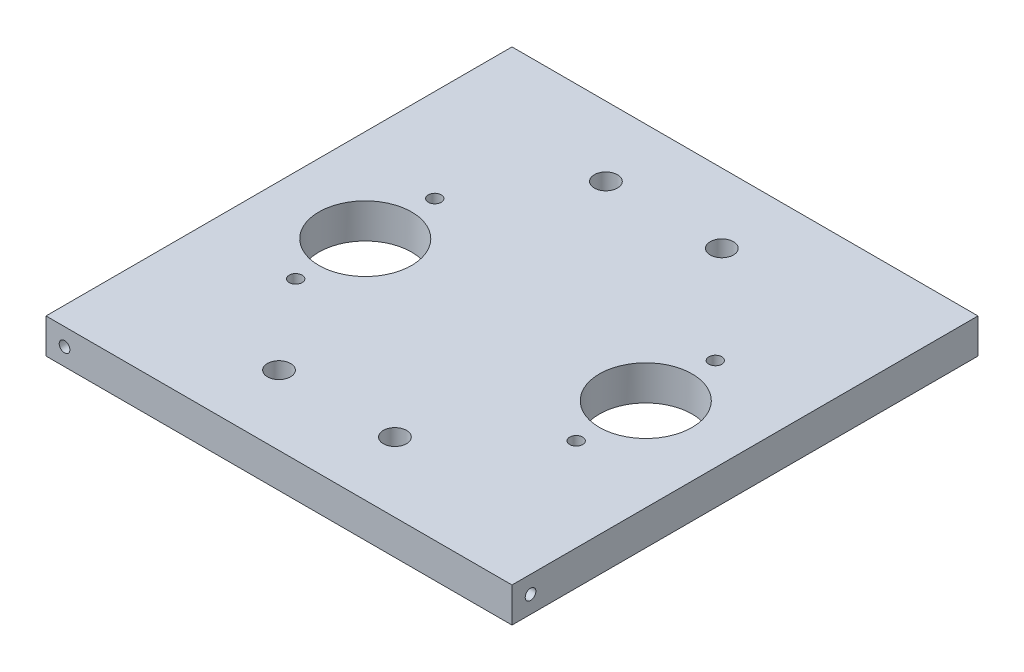
SolidWorks part; units mm, degrees
material "6061 Alloy"
ref_plane "Front" through (0, 0, 0) normal (0, 0, 1) x (1, 0, 0)
ref_plane "Top" through (0, 0, 0) normal (0, 1, 0) x (1, 0, 0)
ref_plane "Right" through (0, 0, 0) normal (1, 0, 0) x (0, 0, -1)
sketch "Sketch1" plane through (0, 0, 0) normal (0, 1, 0) x (1, 0, 0)
  line L1 (0, 0) -> (127.635, 0)
  line L2 (0, 0) -> (0, 127.635)
  line L3 (0, 127.635) -> (127.635, 127.635)
  line L4 (127.635, 0) -> (127.635, 127.635)
  dimension "D1" = 127.635
  dimension "D2" = 127.635
extrude "Main Plate" add sketch "Sketch1" along normal blind 9.525
sketch "Sketch2" plane through (0, 9.525, 0) normal (0, 1, 0) x (1, 0, 0)
  line L0 (0, 127.635) -> (0, 0) construction
  line L1 (127.635, 127.635) -> (0, 127.635) construction
  circle A0 centre (44.7675, 108.585) radius 3.175
  dimension "D1" = 6.35
  dimension "D2" = 44.7675
  dimension "D3" = 19.05
extrude "U-Bolt Hole" cut sketch "Sketch2" against normal blind 12.7
pattern_linear "U-Bolt Pattern" count 2 spacing 31.75 along (1, 0, 0) count 2 spacing 89.535 along (0, 0, 1) of "U-Bolt Hole"
sketch "Sketch3" plane through (0, 9.525, 0) normal (0, 1, 0) x (1, 0, 0)
  line L0 (0, 127.635) -> (0, 0) construction
  line L1 (0, 0) -> (127.635, 0) construction
  circle A0 centre (25.4, 42.9895) radius 1.778
  dimension "D1" = 3.556
  dimension "D2" = 25.4
  dimension "D3" = 42.9895
extrude "Raptor Bolt Hole" cut sketch "Sketch3" against normal blind 12.7
pattern_linear "Raptor Bolt Pattern" count 2 spacing 38.1 along (0, 0, -1) count 2 spacing 76.835 along (1, 0, 0) of "Raptor Bolt Hole"
sketch "Sketch4" plane through (0, 9.525, 0) normal (0, 1, 0) x (1, 0, 0)
  line L0 (0, 127.635) -> (0, 0) construction
  circle A0 centre (25.4, 62.0395) radius 12.7
  dimension "D1" = 25.4
  dimension "D2" = 19.05
  dimension "D3" = 25.4
extrude "Co2 Cylinder Hole" cut sketch "Sketch4" against normal blind 12.7
pattern_linear "Co2 Pattern" count 2 spacing 76.835 along (1, 0, 0) of "Co2 Cylinder Hole"
sketch "Sketch5" plane through (0, 0, 0) normal (0, 0, 1) x (1, 0, 0)
  line L0 (0, 9.525) -> (0, 0) construction
  line L1 (0, 0) -> (127.635, 0) construction
  circle A0 centre (5.08, 4.7625) radius 1.4605
  dimension "D1" = 2.921
  dimension "D2" = 5.08
  dimension "D3" = 4.7625
extrude "Frame attachment hole 1" cut sketch "Sketch5" against normal blind 12.7
sketch "Sketch6" plane through (0, 0, 0) normal (-1, 0, 0) x (0, 0, 1)
  line L2 (-127.635, 0) -> (0, 0) construction
  line L3 (-127.635, 9.525) -> (-127.635, 0) construction
  circle A0 centre (-122.555, 4.7625) radius 1.4605
  dimension "D1" = 2.921
  dimension "D2" = 4.7625
  dimension "D3" = 5.08
extrude "Frame attachment hole 2" cut sketch "Sketch6" against normal blind 12.7
sketch "Sketch7" plane through (0, 0, -127.635) normal (0, 0, -1) x (-1, 0, 0)
  line L2 (-127.635, 0) -> (0, 0) construction
  line L3 (-127.635, 9.525) -> (-127.635, 0) construction
  circle A0 centre (-122.555, 4.7625) radius 1.4605
  dimension "D1" = 2.921
  dimension "D2" = 4.7625
  dimension "D3" = 5.08
extrude "Frame attachment hole 3" cut sketch "Sketch7" against normal blind 12.7
sketch "Sketch8" plane through (127.635, 0, 0) normal (1, 0, 0) x (0, 0, -1)
  line L2 (0, 0) -> (127.635, 0) construction
  line L3 (0, 9.525) -> (0, 0) construction
  circle A0 centre (5.08, 4.7625) radius 1.4605
  dimension "D1" = 2.921
  dimension "D2" = 4.7625
  dimension "D3" = 5.08
extrude "Frame attachment hole 4" cut sketch "Sketch8" against normal blind 12.7
